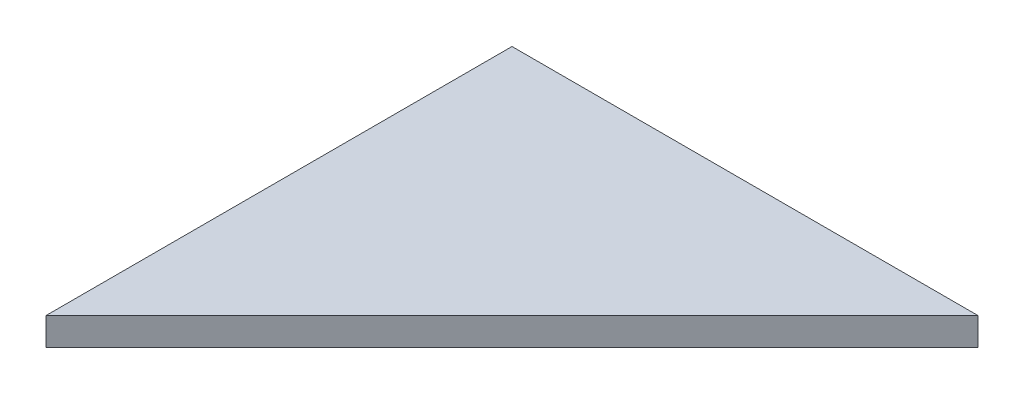
SolidWorks part; units mm, degrees
material "Acrylic (Medium-high impact)"
ref_plane "Front Plane" through (0, 0, 0) normal (0, 0, 1) x (1, 0, 0)
ref_plane "Top Plane" through (0, 0, 0) normal (0, 1, 0) x (1, 0, 0)
ref_plane "Right Plane" through (0, 0, 0) normal (1, 0, 0) x (0, 0, -1)
ref_plane "Plane1" through (0, -113.7049, 0) normal (0, -1, 0) x (-1, 0, 0)
sketch "Sketch1" plane through (0, -113.7049, 0) normal (0, -1, 0) x (-1, 0, 0)
  line L3 (-93.8538, -43.3538) -> (-43.3538, -93.8538)
  line L4 (-43.3538, -93.8538) -> (-43.3538, -43.3538)
  line L5 (-43.3538, -43.3538) -> (-93.8538, -43.3538)
  point P2 (0, 0)
  dimension "D1" = 50.5
extrude "Boss-Extrude1" add sketch "Sketch1" against normal mid plane 3
ref_plane "Plane2" through (80.4015, -80.4015, 0) normal (0.7071, -0.7071, 0) x (-0.7071, -0.7071, 0)
